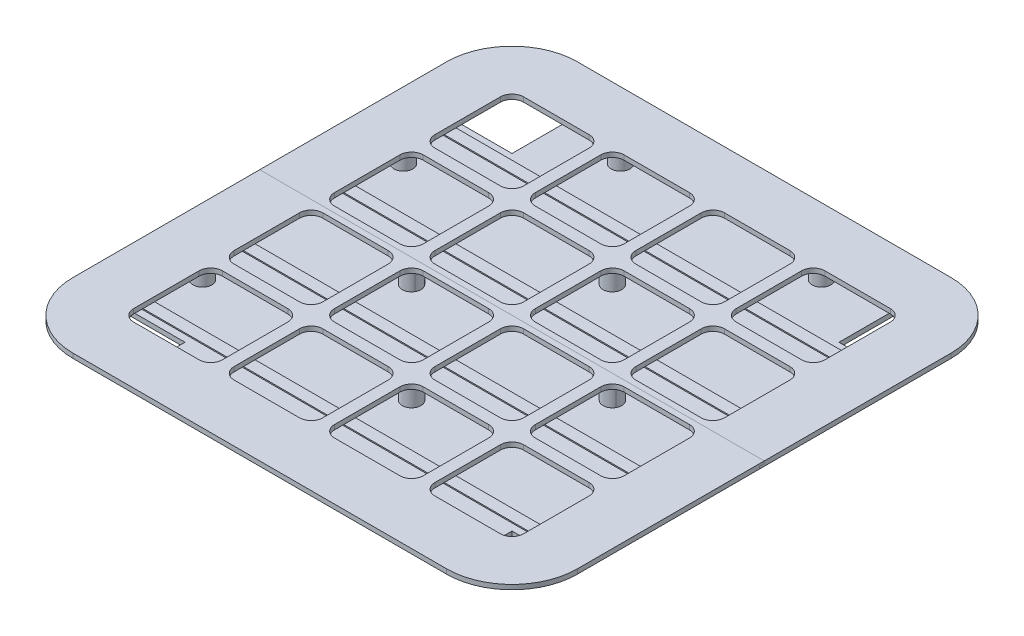
SolidWorks part; units mm, degrees
ref_plane "Front Plane" through (0, 0, 0) normal (0, 0, 1) x (1, 0, 0)
ref_plane "Top Plane" through (0, 0, 0) normal (0, 1, 0) x (1, 0, 0)
ref_plane "Right Plane" through (0, 0, 0) normal (1, 0, 0) x (0, 0, -1)
sketch "Sketch1" plane through (0, 0, 0) normal (0, 1, 0) x (1, 0, 0)
  line L0 (-70, 98) -> (-70, 70)
  line L2 (-98, -70) -> (-98, 70)
  line L4 (98, -70) -> (98, 70)
  line L5 (-98, -70) -> (98, 70) construction
  line L6 (-98, 70) -> (98, -70) construction
  line L7 (-70, -98) -> (70, -98)
  line L9 (-70, 98) -> (70, 98)
  line L11 (-70, -98) -> (70, 98) construction
  line L12 (-70, 98) -> (70, -98) construction
  line L13 (-98, 70) -> (-70, 70)
  line L14 (98, 70) -> (70, 70)
  line L15 (70, 70) -> (70, 98)
  line L16 (70, -98) -> (70, -70)
  line L17 (-70, -98) -> (-70, -70)
  line L18 (70, -70) -> (98, -70)
  line L19 (-70, -70) -> (-98, -70)
  point P0 (0, 0)
  point P6 (0, 0)
  dimension "D1" = 196
  dimension "D2" = 140
  dimension "D3" = 196
  dimension "D4" = 140
  dimension "D5" = 28
  dimension "D6" = 28
  dimension "D7" = 28
  dimension "D8" = 28
extrude "Boss-Extrude1" add sketch "Sketch1" along normal blind 2
sketch "Sketch3" plane through (0, 2, 0) normal (0, 1, 0) x (1, 0, 0)
  line L0 (-35.5, 83.5) -> (-7.5, 83.5)
  line L5 (-40.5, 78.5) -> (-40.5, 50.5)
  line L6 (-35.5, 45.5) -> (-7.5, 45.5)
  line L11 (-2.5, 78.5) -> (-2.5, 50.5)
  line L12 (7.5, 83.5) -> (35.5, 83.5)
  line L13 (-78.5, 83.5) -> (-50.5, 83.5)
  line L14 (-83.5, 78.5) -> (-83.5, 50.5)
  line L15 (-78.5, 45.5) -> (-50.5, 45.5)
  line L16 (-45.5, 78.5) -> (-45.5, 50.5)
  line L17 (2.5, 78.5) -> (2.5, 50.5)
  line L18 (7.5, 45.5) -> (35.5, 45.5)
  line L19 (40.5, 78.5) -> (40.5, 50.5)
  line L20 (50.5, 83.5) -> (78.5, 83.5)
  line L21 (45.5, 78.5) -> (45.5, 50.5)
  line L22 (50.5, 45.5) -> (78.5, 45.5)
  line L23 (83.5, 78.5) -> (83.5, 50.5)
  line L24 (-35.5, 40.5) -> (-7.5, 40.5)
  line L25 (-40.5, 35.5) -> (-40.5, 7.5)
  line L26 (-35.5, 2.5) -> (-7.5, 2.5)
  line L27 (-2.5, 35.5) -> (-2.5, 7.5)
  line L28 (7.5, 40.5) -> (35.5, 40.5)
  line L29 (2.5, 35.5) -> (2.5, 7.5)
  line L30 (7.5, 2.5) -> (35.5, 2.5)
  line L31 (40.5, 35.5) -> (40.5, 7.5)
  line L32 (50.5, 40.5) -> (78.5, 40.5)
  line L33 (45.5, 35.5) -> (45.5, 7.5)
  line L34 (50.5, 2.5) -> (78.5, 2.5)
  line L35 (83.5, 35.5) -> (83.5, 7.5)
  line L36 (-35.5, -2.5) -> (-7.5, -2.5)
  line L37 (-40.5, -7.5) -> (-40.5, -35.5)
  line L38 (-35.5, -40.5) -> (-7.5, -40.5)
  line L39 (-2.5, -7.5) -> (-2.5, -35.5)
  line L40 (7.5, -2.5) -> (35.5, -2.5)
  line L41 (2.5, -7.5) -> (2.5, -35.5)
  line L42 (7.5, -40.5) -> (35.5, -40.5)
  line L43 (40.5, -7.5) -> (40.5, -35.5)
  line L44 (50.5, -2.5) -> (78.5, -2.5)
  line L45 (45.5, -7.5) -> (45.5, -35.5)
  line L46 (50.5, -40.5) -> (78.5, -40.5)
  line L47 (83.5, -7.5) -> (83.5, -35.5)
  line L48 (-35.5, -45.5) -> (-7.5, -45.5)
  line L49 (-40.5, -50.5) -> (-40.5, -78.5)
  line L50 (-35.5, -83.5) -> (-7.5, -83.5)
  line L51 (-2.5, -50.5) -> (-2.5, -78.5)
  line L52 (7.5, -45.5) -> (35.5, -45.5)
  line L53 (2.5, -50.5) -> (2.5, -78.5)
  line L54 (7.5, -83.5) -> (35.5, -83.5)
  line L55 (40.5, -50.5) -> (40.5, -78.5)
  line L56 (50.5, -45.5) -> (78.5, -45.5)
  line L57 (45.5, -50.5) -> (45.5, -78.5)
  line L58 (50.5, -83.5) -> (78.5, -83.5)
  line L59 (83.5, -50.5) -> (83.5, -78.5)
  line L60 (-78.5, 40.5) -> (-50.5, 40.5)
  line L61 (-83.5, 35.5) -> (-83.5, 7.5)
  line L62 (-78.5, 2.5) -> (-50.5, 2.5)
  line L63 (-45.5, 35.5) -> (-45.5, 7.5)
  line L64 (-78.5, -2.5) -> (-50.5, -2.5)
  line L65 (-83.5, -7.5) -> (-83.5, -35.5)
  line L66 (-78.5, -40.5) -> (-50.5, -40.5)
  line L67 (-45.5, -7.5) -> (-45.5, -35.5)
  line L68 (-78.5, -45.5) -> (-50.5, -45.5)
  line L69 (-83.5, -50.5) -> (-83.5, -78.5)
  line L70 (-78.5, -83.5) -> (-50.5, -83.5)
  line L71 (-45.5, -50.5) -> (-45.5, -78.5)
  line L72 (83.5, 64.5) -> (-83.5, 64.5) construction
  line L74 (83.5, 21.5) -> (-83.5, 21.5) construction
  line L76 (83.5, -21.5) -> (-83.5, -21.5) construction
  line L77 (83.5, -64.5) -> (-83.5, -64.5) construction
  line L78 (64.5, 83.5) -> (64.5, -83.5) construction
  line L79 (21.5, 83.5) -> (21.5, -83.5) construction
  line L80 (-21.5, 83.5) -> (-21.5, -83.5) construction
  line L81 (-64.5, 83.5) -> (-64.5, -83.5) construction
  line L82 (80, 108) -> (-80, 108)
  line L86 (-108, 80) -> (-108, 70)
  line L87 (-108, -80) -> (-108, 70)
  line L88 (-80, -108) -> (80, -108)
  line L89 (108, -80) -> (108, 70)
  line L90 (108, 70) -> (108, 80)
  arc A4 (-45.5, 78.5) -> (-50.5, 83.5) centre (-50.5, 78.5) ccw
  arc A5 (-83.5, 78.5) -> (-78.5, 83.5) centre (-78.5, 78.5) cw
  arc A6 (-78.5, 45.5) -> (-83.5, 50.5) centre (-78.5, 50.5) cw
  arc A7 (-45.5, 50.5) -> (-50.5, 45.5) centre (-50.5, 50.5) cw
  arc A8 (-40.5, 78.5) -> (-35.5, 83.5) centre (-35.5, 78.5) cw
  arc A9 (-35.5, 45.5) -> (-40.5, 50.5) centre (-35.5, 50.5) cw
  arc A10 (-2.5, 50.5) -> (-7.5, 45.5) centre (-7.5, 50.5) cw
  arc A11 (-2.5, 78.5) -> (-7.5, 83.5) centre (-7.5, 78.5) ccw
  arc A12 (2.5, 78.5) -> (7.5, 83.5) centre (7.5, 78.5) cw
  arc A13 (7.5, 45.5) -> (2.5, 50.5) centre (7.5, 50.5) cw
  arc A14 (40.5, 50.5) -> (35.5, 45.5) centre (35.5, 50.5) cw
  arc A15 (40.5, 78.5) -> (35.5, 83.5) centre (35.5, 78.5) ccw
  arc A16 (45.5, 78.5) -> (50.5, 83.5) centre (50.5, 78.5) cw
  arc A17 (50.5, 45.5) -> (45.5, 50.5) centre (50.5, 50.5) cw
  arc A18 (83.5, 50.5) -> (78.5, 45.5) centre (78.5, 50.5) cw
  arc A19 (83.5, 78.5) -> (78.5, 83.5) centre (78.5, 78.5) ccw
  arc A20 (-40.5, 35.5) -> (-35.5, 40.5) centre (-35.5, 35.5) cw
  arc A21 (-35.5, 2.5) -> (-40.5, 7.5) centre (-35.5, 7.5) cw
  arc A22 (-2.5, 7.5) -> (-7.5, 2.5) centre (-7.5, 7.5) cw
  arc A23 (-2.5, 35.5) -> (-7.5, 40.5) centre (-7.5, 35.5) ccw
  arc A24 (2.5, 35.5) -> (7.5, 40.5) centre (7.5, 35.5) cw
  arc A25 (7.5, 2.5) -> (2.5, 7.5) centre (7.5, 7.5) cw
  arc A26 (40.5, 7.5) -> (35.5, 2.5) centre (35.5, 7.5) cw
  arc A27 (40.5, 35.5) -> (35.5, 40.5) centre (35.5, 35.5) ccw
  arc A28 (45.5, 35.5) -> (50.5, 40.5) centre (50.5, 35.5) cw
  arc A29 (50.5, 2.5) -> (45.5, 7.5) centre (50.5, 7.5) cw
  arc A30 (83.5, 7.5) -> (78.5, 2.5) centre (78.5, 7.5) cw
  arc A31 (83.5, 35.5) -> (78.5, 40.5) centre (78.5, 35.5) ccw
  arc A32 (-40.5, -7.5) -> (-35.5, -2.5) centre (-35.5, -7.5) cw
  arc A33 (-35.5, -40.5) -> (-40.5, -35.5) centre (-35.5, -35.5) cw
  arc A34 (-2.5, -35.5) -> (-7.5, -40.5) centre (-7.5, -35.5) cw
  arc A35 (-2.5, -7.5) -> (-7.5, -2.5) centre (-7.5, -7.5) ccw
  arc A36 (2.5, -7.5) -> (7.5, -2.5) centre (7.5, -7.5) cw
  arc A37 (7.5, -40.5) -> (2.5, -35.5) centre (7.5, -35.5) cw
  arc A38 (40.5, -35.5) -> (35.5, -40.5) centre (35.5, -35.5) cw
  arc A39 (40.5, -7.5) -> (35.5, -2.5) centre (35.5, -7.5) ccw
  arc A40 (45.5, -7.5) -> (50.5, -2.5) centre (50.5, -7.5) cw
  arc A41 (50.5, -40.5) -> (45.5, -35.5) centre (50.5, -35.5) cw
  arc A42 (83.5, -35.5) -> (78.5, -40.5) centre (78.5, -35.5) cw
  arc A43 (83.5, -7.5) -> (78.5, -2.5) centre (78.5, -7.5) ccw
  arc A44 (-40.5, -50.5) -> (-35.5, -45.5) centre (-35.5, -50.5) cw
  arc A45 (-35.5, -83.5) -> (-40.5, -78.5) centre (-35.5, -78.5) cw
  arc A46 (-2.5, -78.5) -> (-7.5, -83.5) centre (-7.5, -78.5) cw
  arc A47 (-2.5, -50.5) -> (-7.5, -45.5) centre (-7.5, -50.5) ccw
  arc A48 (2.5, -50.5) -> (7.5, -45.5) centre (7.5, -50.5) cw
  arc A49 (7.5, -83.5) -> (2.5, -78.5) centre (7.5, -78.5) cw
  arc A50 (40.5, -78.5) -> (35.5, -83.5) centre (35.5, -78.5) cw
  arc A51 (40.5, -50.5) -> (35.5, -45.5) centre (35.5, -50.5) ccw
  arc A52 (45.5, -50.5) -> (50.5, -45.5) centre (50.5, -50.5) cw
  arc A53 (50.5, -83.5) -> (45.5, -78.5) centre (50.5, -78.5) cw
  arc A54 (83.5, -78.5) -> (78.5, -83.5) centre (78.5, -78.5) cw
  arc A55 (83.5, -50.5) -> (78.5, -45.5) centre (78.5, -50.5) ccw
  arc A56 (-83.5, 35.5) -> (-78.5, 40.5) centre (-78.5, 35.5) cw
  arc A57 (-78.5, 2.5) -> (-83.5, 7.5) centre (-78.5, 7.5) cw
  arc A58 (-45.5, 7.5) -> (-50.5, 2.5) centre (-50.5, 7.5) cw
  arc A59 (-45.5, 35.5) -> (-50.5, 40.5) centre (-50.5, 35.5) ccw
  arc A60 (-83.5, -7.5) -> (-78.5, -2.5) centre (-78.5, -7.5) cw
  arc A61 (-78.5, -40.5) -> (-83.5, -35.5) centre (-78.5, -35.5) cw
  arc A62 (-45.5, -35.5) -> (-50.5, -40.5) centre (-50.5, -35.5) cw
  arc A63 (-45.5, -7.5) -> (-50.5, -2.5) centre (-50.5, -7.5) ccw
  arc A64 (-83.5, -50.5) -> (-78.5, -45.5) centre (-78.5, -50.5) cw
  arc A65 (-78.5, -83.5) -> (-83.5, -78.5) centre (-78.5, -78.5) cw
  arc A66 (-45.5, -78.5) -> (-50.5, -83.5) centre (-50.5, -78.5) cw
  arc A67 (-45.5, -50.5) -> (-50.5, -45.5) centre (-50.5, -50.5) ccw
  arc A74 (-80, 108) -> (-108, 80) centre (-80, 80) ccw
  arc A75 (108, 80) -> (80, 108) centre (80, 80) ccw
  arc A76 (108, -80) -> (80, -108) centre (80, -80) cw
  arc A77 (-80, -108) -> (-108, -80) centre (-80, -80) cw
  dimension "D3" = 24.5
  dimension "D1" = 5
  dimension "D4" = 5
  dimension "D5" = 5
  dimension "D6" = 5
  dimension "D11" = 28
  dimension "D13" = 28
  dimension "D2" = 24.5
  dimension "D7" = 38
  dimension "D8" = 4
  dimension "D10" = 5
  dimension "D12" = 5
  dimension "D14" = 216
  dimension "D9" = 4
extrude "Boss-Extrude3" add sketch "Sketch3" along normal blind 2 from offset 8 separate body
sketch "Sketch7" plane through (0, 10, 0) normal (0, -1, 0) x (1, 0, 0)
  line L0 (-98, 0) -> (98, 0)
  line L1 (0, -98) -> (0, 98)
  line L2 (-64.5, 45.5) -> (-64.5, 40.5) construction
  line L3 (-50.5, 45.5) -> (-78.5, 45.5) construction
  line L4 (-78.5, 40.5) -> (-50.5, 40.5) construction
  line L5 (-45.5, 64.5) -> (-40.5, 64.5) construction
  line L6 (-45.5, 78.5) -> (-45.5, 50.5) construction
  line L7 (-40.5, 50.5) -> (-40.5, 78.5) construction
  line L8 (43, -89.5) -> (43, 89.5)
  line L9 (-43, 89.5) -> (-43, -89.5)
  line L10 (89.5, 43) -> (-89.5, 43)
  line L11 (-89.5, -43) -> (89.5, -43)
  circle A0 centre (-89.5, 43) radius 4
  circle A1 centre (-89.5, 43) radius 2.5
  circle A2 centre (-43, 89.5) radius 4
  circle A3 centre (-43, 89.5) radius 2.5
  circle A4 centre (89.5, 43) radius 4
  circle A5 centre (89.5, 43) radius 2.5
  circle A6 centre (43, 89.5) radius 4
  circle A7 centre (43, 89.5) radius 2.5
  circle A8 centre (43, -89.5) radius 4
  circle A9 centre (43, -89.5) radius 2.5
  circle A10 centre (89.5, -43) radius 4
  circle A11 centre (89.5, -43) radius 2.5
  circle A12 centre (-89.5, -43) radius 4
  circle A13 centre (-89.5, -43) radius 2.5
  circle A14 centre (-43, -89.5) radius 4
  circle A15 centre (-43, -89.5) radius 2.5
  circle A16 centre (43, 0) radius 2.5
  circle A17 centre (43, 0) radius 4
  circle A20 centre (0, -43) radius 4
  circle A21 centre (0, -43) radius 2.5
  circle A22 centre (0, 43) radius 4
  circle A23 centre (0, 43) radius 2.5
  circle A24 centre (-43, 0) radius 4
  circle A25 centre (-43, 0) radius 2.5
  point P4 (0, 0)
  point P8 (0, 0)
  point P17 (-64.5, 43)
  point P27 (-43, 64.5)
  dimension "D3" = 8
  dimension "D4" = 5
  dimension "D7" = 8
  dimension "D8" = 5
  dimension "D11" = 8
  dimension "D12" = 5
  dimension "D13" = 8
  dimension "D14" = 5
  dimension "D15" = 8
  dimension "D16" = 5
  dimension "D17" = 8
  dimension "D18" = 5
  dimension "D1" = 196
  dimension "D2" = 196
  dimension "D5" = 25
  dimension "D6" = 2.5
  dimension "D9" = 25
  dimension "D10" = 2.5
extrude "Boss-Extrude7" add sketch "Sketch7" along normal blind 8 contours A0 A1 | A2 A3 | A6 A7 | A4 A5 | A10 A11 | A8 A9 | A14 A15 | A12 A13 | A25 L9 A24 L0 | A25 L0 A24 L9 | A25 L9 A24 L0 | A25 L0 A24 L9 | A21 L1 A20 L11 | A21 L11 A20 L1 | A21 L1 A20 L11 | A21 L11 A20 L1 | L8 A17 L0 A16 | L0 A17 L8 A16 | L8 A17 L0 A16 | L0 A17 L8 A16 | A23 L1 A22 L10 | A23 L10 A22 L1 | A23 L1 A22 L10 | A23 L10 A22 L1 region at (-40.8943, 10, 2.1057) region at (-40.8943, 10, -2.1057) region at (-45.1057, 10, 2.1057) region at (-45.1057, 10, -2.1057) region at (-93.3869, 10, 43) region at (-45.7484, 10, 92.2484) region at (40.2516, 10, 92.2484) region at (89.5, 10, 46.8869) region at (89.5, 10, -39.1131) region at (45.7484, 10, -86.7516) region at (-40.2516, 10, -86.7516) region at (-93.3869, 10, -43) region at (40.8943, 10, 2.1057) region at (40.8943, 10, -2.1057) region at (2.1057, 10, -40.8943) region at (-2.1057, 10, -40.8943) region at (-2.1057, 10, 40.8943) region at (2.1057, 10, 40.8943) region at (45.1057, 10, 2.1057) region at (45.1057, 10, -2.1057) region at (2.1057, 10, -45.1057) region at (-2.1057, 10, -45.1057) region at (-2.1057, 10, 45.1057) region at (2.1057, 10, 45.1057)
sketch "Sketch6" plane through (0, 2, 0) normal (0, 1, 0) x (1, 0, 0)
  line L0 (-98, 64.5) -> (98, 64.5) construction
  line L1 (-98, 70) -> (-98, -70) construction
  line L2 (98, -70) -> (98, 70) construction
  line L3 (-98, 21.5) -> (98, 21.5) construction
  line L4 (-98, -21.5) -> (98, -21.5) construction
  line L5 (-98, -64.5) -> (98, -64.5) construction
  line L6 (-70, 70) -> (-98, 70) construction
  line L7 (-98, -70) -> (-70, -70) construction
  line L9 (-98, 62) -> (98, 62)
  line L10 (-98, 62) -> (-98, 67)
  line L11 (-98, 67) -> (98, 67)
  line L12 (98, 62) -> (98, 67)
  line L13 (-98, 62) -> (98, 67) construction
  line L14 (-98, 67) -> (98, 62) construction
  line L15 (-98, 19) -> (98, 19)
  line L16 (-98, 19) -> (-98, 24)
  line L17 (-98, 24) -> (98, 24)
  line L18 (98, 19) -> (98, 24)
  line L19 (-98, 19) -> (98, 24) construction
  line L20 (-98, 24) -> (98, 19) construction
  line L21 (-98, -24) -> (98, -24)
  line L22 (-98, -24) -> (-98, -19)
  line L23 (-98, -19) -> (98, -19)
  line L24 (98, -24) -> (98, -19)
  line L25 (-98, -24) -> (98, -19) construction
  line L26 (-98, -19) -> (98, -24) construction
  line L27 (-98, -67) -> (98, -67)
  line L28 (-98, -67) -> (-98, -62)
  line L29 (-98, -62) -> (98, -62)
  line L30 (98, -67) -> (98, -62)
  line L31 (-98, -67) -> (98, -62) construction
  line L32 (-98, -62) -> (98, -67) construction
  point P16 (0, 64.5)
  point P21 (0, 21.5)
  point P26 (0, -21.5)
  point P31 (0, -64.5)
  dimension "D1" = 5.5
  dimension "D2" = 43
  dimension "D3" = 5.5
  dimension "D4" = 43
  dimension "D5" = 5
  dimension "D6" = 5
  dimension "D7" = 5
  dimension "D8" = 5
extrude "Boss-Extrude6" add sketch "Sketch6" along normal blind 0.5
extrude "Cut-Extrude1" cut sketch "Sketch7<6>" along normal blind 10 contours A3 | A1 | A13 | A15 | A9 | A11 | A5 | L0 A16 L8 | L8 A16 L0 | L0 A16 L8 | L8 A16 L0 | L11 A21 L1 | L1 A21 L11 | L11 A21 L1 | L1 A21 L11 | L0 A25 L9 | L9 A25 L0 | L0 A25 L9 | L9 A25 L0 | L1 A23 L10 | L10 A23 L1 | L10 A23 L1 | L1 A23 L10 | A7 region at (-41.939, 10, -1.061) region at (-41.939, 10, 1.061) region at (-44.061, 10, -1.061) region at (-44.061, 10, 1.061) region at (-91.9293, 10, 43) region at (-44.7178, 10, 91.2178) region at (41.2822, 10, 91.2178) region at (89.5, 10, 45.4293) region at (89.5, 10, -40.5707) region at (44.7178, 10, -87.7822) region at (-41.2822, 10, -87.7822) region at (-91.9293, 10, -43) region at (41.939, 10, 1.061) region at (41.939, 10, -1.061) region at (1.061, 10, -41.939) region at (-1.061, 10, -41.939) region at (-1.061, 10, 41.939) region at (1.061, 10, 41.939) region at (44.061, 10, 1.061) region at (44.061, 10, -1.061) region at (1.061, 10, -44.061) region at (-1.061, 10, -44.061) region at (-1.061, 10, 44.061) region at (1.061, 10, 44.061)
sketch "Sketch7<6>" plane through (0, 10, 0) normal (0, -1, 0) x (1, 0, 0) same geometry as "Sketch7"
sketch "Sketch9" plane through (108, 0, 0) normal (1, 0, 0) x (0, 0, -1)
  line L0 (0, 11) -> (0, 12)
  line L3 (-80, 12) -> (80, 12) construction
  line L7 (0, 11) -> (-2, 11)
  line L8 (-2, 11) -> (-2, 10)
  line L9 (-2, 10) -> (-2, 2)
  line L10 (-19, 2) -> (19, 2) construction
  dimension "D1" = 2
  dimension "D2" = 1
  dimension "D3" = 1
split "Split1" trim tools "Sketch9" bodies to split 118 resulting bodies 136 137
sketch "Sketch10" plane through (0, 2, 0) normal (0, 1, 0) x (1, 0, 0)
  line L1 (93, -14) -> (-93, -14)
  line L2 (93, -14) -> (93, 14)
  line L3 (93, 14) -> (-93, 14)
  line L4 (-93, -14) -> (-93, 14)
  line L5 (93, -14) -> (-93, 14) construction
  line L6 (93, 14) -> (-93, -14) construction
  line L7 (-98, 19) -> (98, 19) construction
  line L8 (-98, 19) -> (-98, -19) construction
  line L9 (-33, 14) -> (-2.9001, 4.8788)
  line L10 (-33, -14) -> (-53, -14)
  line L11 (-33, -14) -> (-33, 14)
  line L12 (-33, 14) -> (-53, 14)
  line L13 (-53, -14) -> (-53, 14)
  line L14 (-33, -14) -> (-53, 14) construction
  line L15 (-33, 14) -> (-53, -14) construction
  line L16 (53, -14) -> (33, -14)
  line L17 (53, -14) -> (53, 14)
  line L18 (53, 14) -> (33, 14)
  line L19 (33, -14) -> (33, 14)
  line L20 (53, -14) -> (33, 14) construction
  line L21 (53, 14) -> (33, -14) construction
  line L28 (53, 14) -> (93, 4)
  line L29 (53, -14) -> (93, -4)
  line L67 (93, -57) -> (-93, -57)
  line L68 (93, -57) -> (93, -29)
  line L69 (93, -29) -> (-93, -29)
  line L70 (-93, -57) -> (-93, -29)
  line L71 (93, -57) -> (-93, -29) construction
  line L72 (93, -29) -> (-93, -57) construction
  line L73 (10, -57) -> (-10, -57)
  line L74 (10, -57) -> (10, -29)
  line L75 (10, -29) -> (-10, -29)
  line L76 (-10, -57) -> (-10, -29)
  line L77 (10, -57) -> (-10, -29) construction
  line L78 (10, -29) -> (-10, -57) construction
  line L79 (-80, -57) -> (-80, -29)
  line L80 (80, -57) -> (80, -29)
  line L82 (-80, -29) -> (-47.7472, -38.2151)
  line L83 (-10, -57) -> (-42.2528, -47.7849)
  line L84 (-80, -57) -> (-47.7472, -47.7849)
  line L85 (10, -57) -> (42.2528, -47.7849)
  line L88 (47.7472, -47.7849) -> (80, -57)
  line L89 (-98, -24) -> (98, -24) construction
  line L90 (-98, -24) -> (-98, -62) construction
  line L91 (-43, 72) -> (43, 72)
  line L92 (43, 72) -> (4.2173, 90.0385)
  line L93 (-4.2173, 90.0385) -> (-43, 72)
  line L94 (-65, 86) -> (-65, 72)
  line L95 (-65, 72) -> (-54, 72)
  line L96 (-52.4, 75.2) -> (-61.4, 87.2)
  line L97 (98, 67) -> (-98, 67) construction
  line L98 (-70, 98) -> (-70, 70) construction
  line L99 (54, 72) -> (65, 72)
  line L100 (65, 72) -> (65, 86)
  line L101 (61.4, 87.2) -> (52.4, 75.2)
  line L102 (70, 70) -> (70, 98) construction
  line L112 (-43, -72) -> (43, -72)
  line L113 (43, -72) -> (4.2173, -90.0385)
  line L114 (-4.2173, -90.0385) -> (-43, -72)
  line L115 (54, -72) -> (65, -72)
  line L116 (65, -72) -> (65, -86)
  line L117 (61.4, -87.2) -> (52.4, -75.2)
  line L118 (-65, -72) -> (-65, -86)
  line L119 (-61.4, -87.2) -> (-52.4, -75.2)
  line L120 (-54, -72) -> (-65, -72)
  line L121 (70, -98) -> (70, -70) construction
  line L122 (-98, -67) -> (98, -67) construction
  line L123 (-98, -67) -> (98, -67) construction
  line L124 (-42.2528, -38.2151) -> (-10, -29)
  line L125 (80, -29) -> (47.7472, -38.2151)
  line L126 (42.2528, -38.2151) -> (10, -29)
  line L127 (93, 29) -> (-93, 29)
  line L128 (93, 29) -> (93, 57)
  line L129 (93, 57) -> (-93, 57)
  line L130 (-93, 29) -> (-93, 57)
  line L131 (93, 29) -> (-93, 57) construction
  line L132 (93, 57) -> (-93, 29) construction
  line L133 (12.3589, 29) -> (-12.3589, 29)
  line L134 (12.3589, 29) -> (12.3589, 57)
  line L135 (12.3589, 57) -> (-12.3589, 57)
  line L136 (-12.3589, 29) -> (-12.3589, 57)
  line L137 (12.3589, 29) -> (-12.3589, 57) construction
  line L138 (12.3589, 57) -> (-12.3589, 29) construction
  line L139 (-82.3589, 29) -> (-82.3589, 57)
  line L140 (82.3589, 29) -> (82.3589, 57)
  line L141 (-82.3589, 57) -> (-50.1061, 47.7849)
  line L142 (-12.3589, 29) -> (-44.6117, 38.2151)
  line L143 (-82.3589, 29) -> (-50.1061, 38.2151)
  line L144 (12.3589, 29) -> (44.6117, 38.2151)
  line L145 (50.1061, 38.2151) -> (82.3589, 29)
  line L146 (-44.6117, 47.7849) -> (-12.3589, 57)
  line L147 (82.3589, 57) -> (50.1061, 47.7849)
  line L148 (44.6117, 47.7849) -> (12.3589, 57)
  line L149 (-98, 62) -> (98, 62) construction
  line L150 (-98, 62) -> (-98, 24) construction
  line L151 (98, 24) -> (98, 62) construction
  line L152 (2.9001, 4.8788) -> (33, 14)
  line L153 (33, -14) -> (2.9001, -4.8788)
  line L154 (-2.9001, -4.8788) -> (-33, -14)
  line L155 (-53, -14) -> (-93, -4)
  line L156 (-53, 14) -> (-93, 4)
  arc A1 (4.2173, -90.0385) -> (-4.2173, -90.0385) centre (0, -80.9713) cw
  circle A2 centre (0, -43) radius 2.5 construction
  arc A3 (47.7472, -47.7849) -> (42.2528, -47.7849) centre (45, -57.4002) ccw
  arc A4 (47.7472, -38.2151) -> (42.2528, -38.2151) centre (45, -28.5998) cw
  arc A5 (-42.2528, -47.7849) -> (-47.7472, -47.7849) centre (-45, -57.4002) ccw
  arc A6 (-42.2528, -38.2151) -> (-47.7472, -38.2151) centre (-45, -28.5998) cw
  arc A7 (2.9001, -4.8788) -> (-2.9001, -4.8788) centre (0, -14.4491) ccw
  arc A8 (2.9001, 4.8788) -> (-2.9001, 4.8788) centre (0, 14.4491) cw
  arc A9 (4.2173, 90.0385) -> (-4.2173, 90.0385) centre (0, 80.9713) ccw
  arc A10 (50.1061, 38.2151) -> (44.6117, 38.2151) centre (47.3589, 28.5998) ccw
  arc A11 (50.1061, 47.7849) -> (44.6117, 47.7849) centre (47.3589, 57.4002) cw
  arc A12 (-44.6117, 47.7849) -> (-50.1061, 47.7849) centre (-47.3589, 57.4002) cw
  arc A13 (-44.6117, 38.2151) -> (-50.1061, 38.2151) centre (-47.3589, 28.5998) ccw
  arc A14 (-52.4, -75.2) -> (-54, -72) centre (-54, -74) ccw
  arc A15 (-61.4, -87.2) -> (-65, -86) centre (-63, -86) cw
  arc A16 (54, -72) -> (52.4, -75.2) centre (54, -74) ccw
  arc A17 (65, -86) -> (61.4, -87.2) centre (63, -86) cw
  arc A18 (65, 86) -> (61.4, 87.2) centre (63, 86) ccw
  arc A19 (52.4, 75.2) -> (54, 72) centre (54, 74) ccw
  arc A20 (-52.4, 75.2) -> (-54, 72) centre (-54, 74) cw
  arc A21 (-61.4, 87.2) -> (-65, 86) centre (-63, 86) ccw
  point P0 (0, 0)
  point P10 (-43, 0)
  point P16 (43, 0)
  point P22 (0, 43)
  point P30 (0, 43)
  point P40 (12.3589, 43)
  point P48 (0, -43)
  point P55 (0, -43)
  point P65 (10, -43)
  point P110 (0, -92)
  point P113 (45, -47)
  point P116 (45, -39)
  point P119 (-45, -47)
  point P122 (-45, -39)
  point P125 (0, -4)
  point P128 (0, 4)
  point P131 (0, 92)
  point P134 (47.3589, 39)
  point P137 (47.3589, 47)
  point P140 (-47.3589, 47)
  point P143 (-47.3589, 39)
  point P146 (-50, -72)
  point P149 (-65, -92)
  point P152 (50, -72)
  point P155 (65, -92)
  point P158 (65, 92)
  point P161 (50, 72)
  point P164 (-50, 72)
  point P167 (-65, 92)
  dimension "D5" = 8
  dimension "D22" = 5
  dimension "D8" = 70
  dimension "D60" = 10
  dimension "D61" = 2
  dimension "D1" = 5
  dimension "D2" = 5
  dimension "D3" = 20
  dimension "D4" = 20
  dimension "D6" = 10
  dimension "D7" = 10
  dimension "D9" = 35
  dimension "D10" = 20
  dimension "D11" = 0
  dimension "D12" = 5
  dimension "D13" = 5
  dimension "D14" = 20
  dimension "D15" = 5
  dimension "D16" = 20
  dimension "D17" = 5
  dimension "D18" = 5
  dimension "D19" = 20
  dimension "D20" = 5
  dimension "D21" = 5
  dimension "D23" = 20
  dimension "D24" = 20
  dimension "D25" = 20
  dimension "D26" = 86
  dimension "D27" = 43
  dimension "D28" = 70
  dimension "D29" = 70
  dimension "D30" = 86
  dimension "D31" = 43
  dimension "D32" = 15
  dimension "D33" = 15
  dimension "D34" = 15
  dimension "D35" = 15
  dimension "D36" = 8
  dimension "D37" = 10
  dimension "D38" = 10
  dimension "D39" = 70
  dimension "D40" = 35
  dimension "D41" = 70
  dimension "D42" = 35
  dimension "D43" = 35
  dimension "D44" = 8
  dimension "D45" = 10
  dimension "D46" = 10
  dimension "D47" = 70
  dimension "D48" = 35
  dimension "D49" = 35
  dimension "D50" = 8
  dimension "D51" = 10
  dimension "D52" = 10
  dimension "D53" = 5
  dimension "D54" = 5
  dimension "D55" = 5
  dimension "D56" = 8
  dimension "D57" = 10
  dimension "D58" = 8
  dimension "D59" = 8
